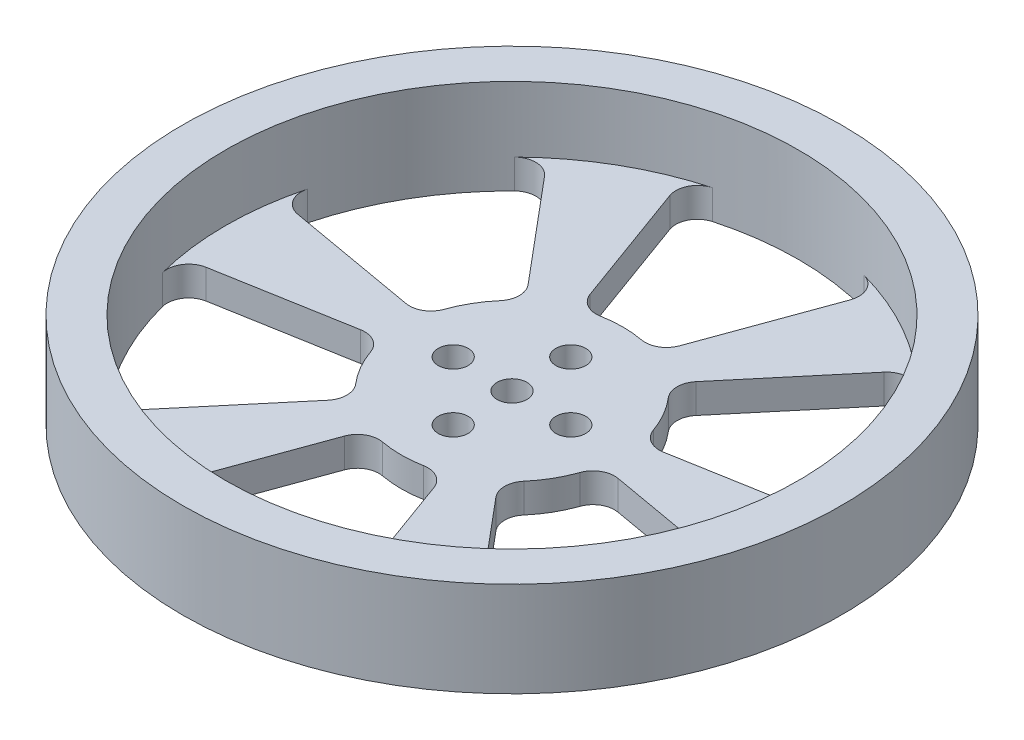
SolidWorks part; units mm, degrees
material "6061-T6 (SS)"
ref_plane "Front Plane" through (0, 0, 0) normal (0, 0, 1) x (1, 0, 0)
ref_plane "Top Plane" through (0, 0, 0) normal (0, 1, 0) x (1, 0, 0)
ref_plane "Right Plane" through (0, 0, 0) normal (1, 0, 0) x (0, 0, -1)
sketch "Sketch1" plane through (0, 0, 0) normal (0, 1, 0) x (1, 0, 0)
  circle A0 centre (0, 0) radius 24.257
  dimension "D1" = 48.514
extrude "Boss-Extrude1" add sketch "Sketch1" along normal blind 4.445
hole_wizard "M2 Clearance Hole1" positions "Sketch3" profile "Sketch2" hole size "M2" standard "ISO" end condition through all
sketch "Sketch3" plane through (0, 4.445, 0) normal (0, 1, 0) x (1, 0, 0)
  line L1 (0, -4.3285) -> (4.3285, 0) construction
  line L2 (0, -4.3285) -> (-4.3285, 0) construction
  line L3 (-4.3285, 0) -> (0, 4.3285) construction
  line L4 (4.3285, 0) -> (0, 4.3285) construction
  line L5 (0, -4.3285) -> (0, 4.3285) construction
  line L6 (-4.3285, 0) -> (4.3285, 0) construction
  point P5 (0, 0)
  point P6 (0, 4.3285)
  point P73 (0, -4.3285)
  point P74 (-4.3285, 0)
  point P75 (4.3285, 0)
  dimension "D1" = 6.1214
sketch "Sketch2" plane through (0, 4.445, 0) normal (1, 0, 0) x (0, 0, 1)
  line L0 (0, 0) -> (0, 4.445)
  line L1 (0, 4.445) -> (1.1, 4.445)
  line L2 (1.1, 4.445) -> (1.1, 0)
  line L5 (1.1, 0) -> (0, 0)
  line L11 (0, -6.35) -> (0, 107.95) construction
  dimension "Thru Hole Dia." = 2.2
  dimension "Thru Hole Depth" = 4.445
sketch "Sketch4" plane through (0, 4.445, 0) normal (0, 1, 0) x (1, 0, 0)
  circle A0 centre (0, 0) radius 21.082
  circle A1 centre (0, 0) radius 24.257 construction
  dimension "D1" = 3.175
extrude "Cut-Extrude1" cut sketch "Sketch4" against normal offset from surface (2.286 mm away) 2.159 up to face at (0, 0, 1.1)
sketch "Sketch5" plane through (0, 2.159, 0) normal (0, 1, 0) x (1, 0, 0)
  line L0 (-2.7908, 7.6677) -> (-7.2105, 19.8106)
  line L1 (2.7908, 7.6677) -> (7.2105, 19.8106)
  line L2 (5.5816, 6.6519) -> (0, 8.6834) construction
  line L3 (0, 8.6834) -> (-5.5816, 6.6519) construction
  line L4 (0, 0) -> (0, 21.082) construction
  line L5 (5.245, 6.2507) -> (13.5512, 16.1497)
  line L6 (8.0358, 1.4169) -> (20.7617, 3.6609)
  line L7 (8.5515, -1.5079) -> (7.5201, 4.3417) construction
  line L8 (7.5201, 4.3417) -> (2.9699, 8.1598) construction
  line L9 (0, 0) -> (18.2575, 10.541) construction
  line L10 (8.0358, -1.4169) -> (20.7617, -3.6609)
  line L11 (5.245, -6.2507) -> (13.5512, -16.1497)
  line L12 (2.9699, -8.1598) -> (7.5201, -4.3417) construction
  line L13 (7.5201, -4.3417) -> (8.5515, 1.5079) construction
  line L14 (0, 0) -> (18.2575, -10.541) construction
  line L15 (2.7908, -7.6677) -> (7.2105, -19.8106)
  line L16 (-2.7908, -7.6677) -> (-7.2105, -19.8106)
  line L17 (-5.5816, -6.6519) -> (0, -8.6834) construction
  line L18 (0, -8.6834) -> (5.5816, -6.6519) construction
  line L19 (0, 0) -> (0, -21.082) construction
  line L20 (-5.245, -6.2507) -> (-13.5512, -16.1497)
  line L21 (-8.0358, -1.4169) -> (-20.7617, -3.6609)
  line L22 (-8.5515, 1.5079) -> (-7.5201, -4.3417) construction
  line L23 (-7.5201, -4.3417) -> (-2.9699, -8.1598) construction
  line L24 (0, 0) -> (-18.2575, -10.541) construction
  line L25 (-8.0358, 1.4169) -> (-20.7617, 3.6609)
  line L26 (-5.245, 6.2507) -> (-13.5512, 16.1497)
  line L27 (-2.9699, 8.1598) -> (-7.5201, 4.3417) construction
  line L28 (-7.5201, 4.3417) -> (-8.5515, -1.5079) construction
  line L29 (0, 0) -> (-18.2575, 10.541) construction
  arc A0 (2.7908, 7.6677) -> (-2.7908, 7.6677) centre (0, 0) ccw
  arc A1 (7.2105, 19.8106) -> (-7.2105, 19.8106) centre (0, 0) ccw
  circle A2 centre (0, 0) radius 21.082 construction
  arc A3 (8.0358, 1.4169) -> (5.245, 6.2507) centre (0, 0) ccw
  arc A4 (20.7617, 3.6609) -> (13.5512, 16.1497) centre (0, 0) ccw
  arc A5 (5.245, -6.2507) -> (8.0358, -1.4169) centre (0, 0) ccw
  arc A6 (13.5512, -16.1497) -> (20.7617, -3.6609) centre (0, 0) ccw
  arc A7 (-2.7908, -7.6677) -> (2.7908, -7.6677) centre (0, 0) ccw
  arc A8 (-7.2105, -19.8106) -> (7.2105, -19.8106) centre (0, 0) ccw
  arc A9 (-8.0358, -1.4169) -> (-5.245, -6.2507) centre (0, 0) ccw
  arc A10 (-20.7617, -3.6609) -> (-13.5512, -16.1497) centre (0, 0) ccw
  arc A11 (-5.245, 6.2507) -> (-8.0358, 1.4169) centre (0, 0) ccw
  arc A12 (-13.5512, 16.1497) -> (-20.7617, 3.6609) centre (0, 0) ccw
  point P13 (2.7908, 7.6677)
  point P16 (-2.7908, 7.6677)
  point P23 (8.0358, 1.4169)
  point P26 (5.245, 6.2507)
  point P33 (5.245, -6.2507)
  point P36 (8.0358, -1.4169)
  point P43 (-2.7908, -7.6677)
  point P46 (2.7908, -7.6677)
  point P53 (-8.0358, -1.4169)
  point P56 (-5.245, -6.2507)
  point P63 (-5.245, 6.2507)
  point P66 (-8.0358, 1.4169)
  point P67 (0, 0)
  dimension "D1" = 16.3195
  dimension "D2" = 40
  dimension "D3" = 6
extrude "Cut-Extrude2" cut sketch "Sketch5" against normal through all
fillet "Fillet1" radius 1.5875 24 edges at (-7.2105, 1.0795, 19.8106) (-13.5512, 1.0795, 16.1497) (7.2105, 1.0795, 19.8106) (-5.245, 1.0795, 6.2507) (2.7908, 1.0795, 7.6677) (-8.0358, 1.0795, 1.4169) (-2.7908, 1.0795, 7.6677) (-20.7617, 1.0795, 3.6609) (8.0358, 1.0795, 1.4169) (5.245, 1.0795, 6.2507) (13.5512, 1.0795, 16.1497) (20.7617, 1.0795, 3.6609) (20.7617, 1.0795, -3.6609) (13.5512, 1.0795, -16.1497) (8.0358, 1.0795, -1.4169) (5.245, 1.0795, -6.2507) (2.7908, 1.0795, -7.6677) (-2.7908, 1.0795, -7.6677) (-5.245, 1.0795, -6.2507) (-8.0358, 1.0795, -1.4169) (-20.7617, 1.0795, -3.6609) (-13.5512, 1.0795, -16.1497) (-7.2105, 1.0795, -19.8106) (7.2105, 1.0795, -19.8106)
sketch "Sketch6" plane through (0, 4.445, 0) normal (0, 1, 0) x (1, 0, 0)
  circle A0 centre (0, 0) radius 21.082 construction
  circle A1 centre (0, 0) radius 24.257
  circle A2 centre (0, 0) radius 24.257
  circle A3 centre (0, 0) radius 21.082
  dimension "D1" = 0
extrude "Boss-Extrude2" add sketch "Sketch6" along normal blind 2.54
